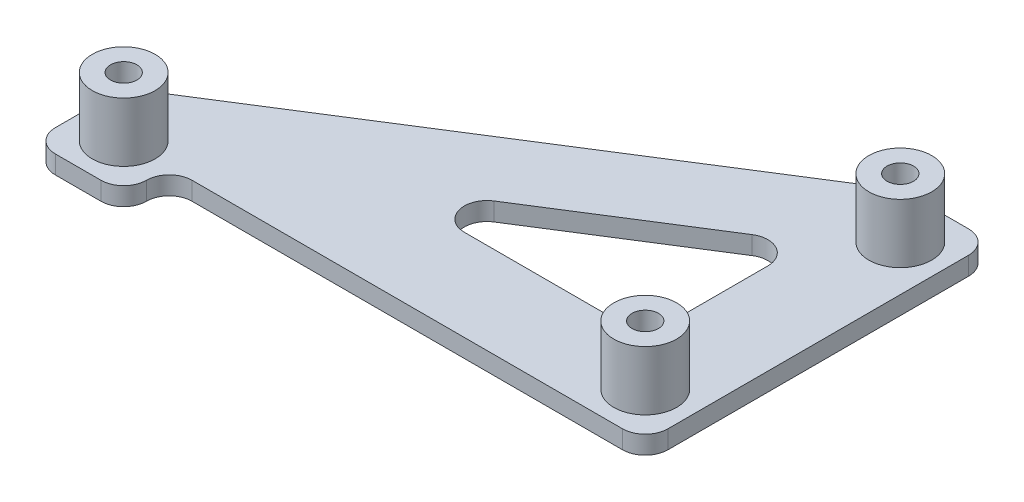
SolidWorks part; units mm, degrees
ref_plane "Front Plane" through (0, 0, 0) normal (0, 0, 1) x (1, 0, 0)
ref_plane "Top Plane" through (0, 0, 0) normal (0, 1, 0) x (1, 0, 0)
ref_plane "Right Plane" through (0, 0, 0) normal (1, 0, 0) x (0, 0, -1)
sketch "Sketch1" plane through (0, 0, 0) normal (0, 1, 0) x (1, 0, 0)
  line L0 (0, -4.675) -> (0, 4.675) construction
  circle A0 centre (0, 0) radius 1.45
  circle A1 centre (-52.25, 5) radius 1.45
  circle A2 centre (0, -28) radius 1.45
  circle A3 centre (-52.25, 5) radius 3.45
  circle A4 centre (0, 0) radius 3.45
  circle A5 centre (0, -28) radius 3.45
  dimension "D1" = 52.25
  dimension "D2" = 28
  dimension "D3" = 5
  dimension "D4" = 2.9
  dimension "D5" = 2
extrude "Boss-Extrude1" add sketch "Sketch1" along normal blind 8.5
sketch "Sketch2" plane through (0, 0, 0) normal (0, 1, 0) x (1, 0, 0)
  line L0 (5, 5) -> (5, -33)
  line L1 (5, -33) -> (-5, -33)
  line L2 (-5, -33) -> (-57.25, 0)
  line L3 (-57.25, 0) -> (-57.25, 10)
  line L5 (-57.25, 0) -> (-47.25, 10) construction
  line L6 (-57.25, 10) -> (-47.25, 0) construction
  line L7 (-4.675, 0) -> (4.675, 0) construction
  line L8 (-57.25, 10) -> (-47.25, 10)
  line L9 (-47.25, 10) -> (-47.25, 5)
  line L10 (-47.25, 5) -> (5, 5)
  line L11 (5, 5) -> (-5, -5) construction
  line L12 (5, -5) -> (-5, 5) construction
  line L13 (5, -33) -> (-5, -23) construction
  line L14 (-33.5, -5) -> (-5, -23)
  line L15 (-5, -23) -> (-5, -5)
  line L16 (-5, -5) -> (-33.5, -5)
  line L19 (-5, -33) -> (5, -23) construction
  line L20 (-52.25, 5) -> (-47.25, 5) construction
  line L21 (0, -28) -> (5, -28) construction
  circle A0 centre (-52.25, 5) radius 1.45 construction
  circle A1 centre (0, -28) radius 1.45 construction
  circle A3 centre (0, 0) radius 1.45 construction
  circle A4 centre (-52.25, 5) radius 1.45
  circle A5 centre (0, -28) radius 1.45
  circle A6 centre (0, 0) radius 1.45
  point P18 (0, 0)
  point P19 (0, 0)
  point P20 (0, -28)
  point P23 (-52.25, 5)
  point P26 (-52.25, 5)
  point P28 (0, -28)
extrude "Boss-Extrude2" add sketch "Sketch2" along normal blind 2
fillet "Fillet2" radius 2.5 10 edges at (-5, 1, 33) (-57.25, 1, 0) (-57.25, 1, -10) (-47.25, 1, -5) (5, 1, -5) (5, 1, 33) (-47.25, 1, -10) (-33.5, 1, 5) (-5, 1, 5) (-5, 1, 23)
mirror "Mirror1" about plane through (0, 0, 0) normal (0, 0, 1) of bodies 104
delete or keep bodies "Body-Delete/Keep 1" type delete bodies bodies 104
